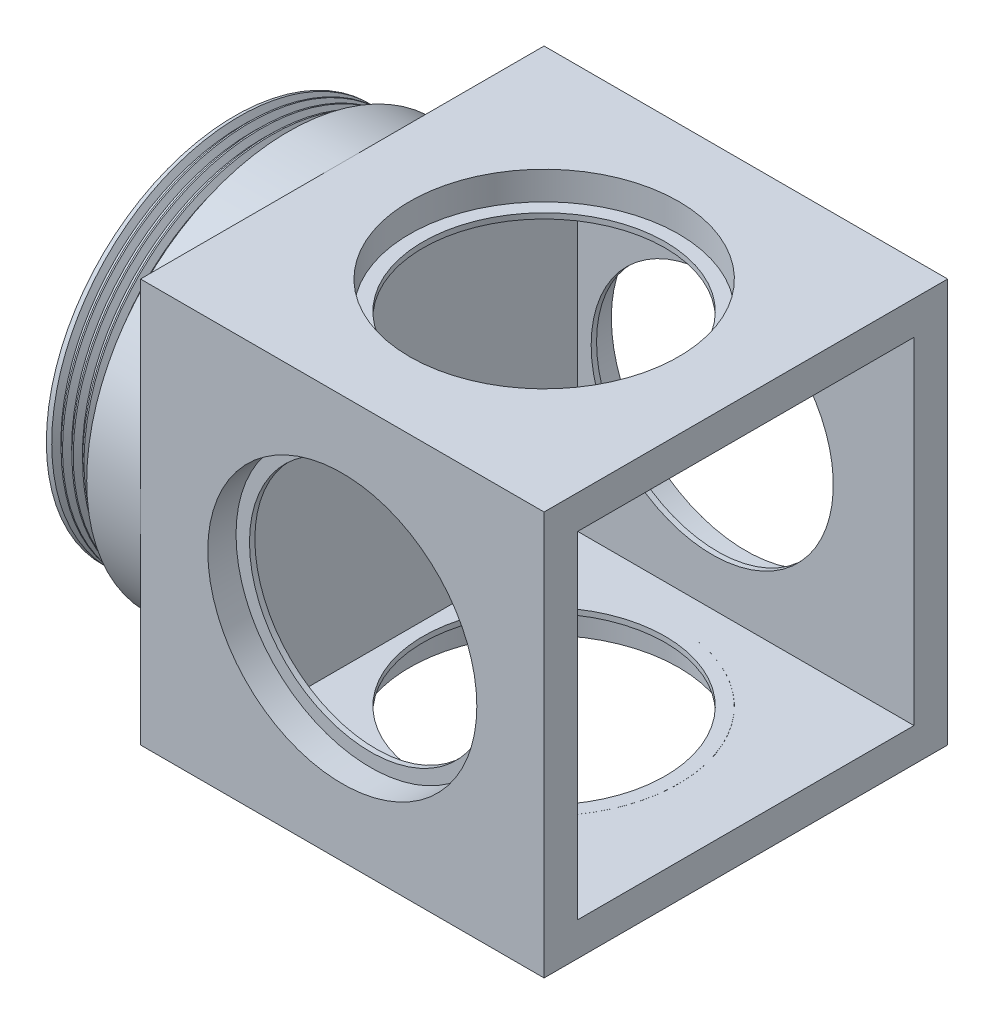
SolidWorks part; units mm, degrees
ref_plane "Front Plane" through (0, 0, 0) normal (0, 0, 1) x (1, 0, 0)
ref_plane "Top Plane" through (0, 0, 0) normal (0, 1, 0) x (1, 0, 0)
ref_plane "Right Plane" through (0, 0, 0) normal (1, 0, 0) x (0, 0, -1)
sketch "Sketch1" plane through (0, 0, 0) normal (0, 0, 1) x (1, 0, 0)
  line L1 (-37.5, -37.5) -> (37.5, -37.5)
  line L2 (-37.5, -37.5) -> (-37.5, 37.5)
  line L3 (-37.5, 37.5) -> (37.5, 37.5)
  line L4 (37.5, -37.5) -> (37.5, 37.5)
  line L5 (-37.5, -37.5) -> (37.5, 37.5) construction
  line L6 (-37.5, 37.5) -> (37.5, -37.5) construction
  line L11 (-25, -25) -> (25, 25) construction
  line L12 (-25, 25) -> (25, -25) construction
  circle A1 centre (0, 0) radius 25
  point P0 (0, 0)
  point P6 (0, 0)
  dimension "D3" = 50
  dimension "D1" = 75
  dimension "D2" = 50
extrude "Boss-Extrude1" add sketch "Sketch1" along normal mid plane 75
sketch "Sketch2" plane through (0, 37.5, 0) normal (0, 1, 0) x (1, 0, 0)
  circle A0 centre (0.0169, 0) radius 25
  point P0 (0, 0)
  dimension "D2" = 50
extrude "Cut-Extrude1" cut sketch "Sketch2" against normal up to surface (75 mm away) up to face at (0, -37.5, 0)
sketch "Sketch3" plane through (37.5, 0, 0) normal (1, 0, 0) x (0, 0, -1)
  line L1 (-31.25, -31.25) -> (31.25, -31.25)
  line L2 (-31.25, -31.25) -> (-31.25, 31.25)
  line L3 (-31.25, 31.25) -> (31.25, 31.25)
  line L4 (31.25, -31.25) -> (31.25, 31.25)
  line L5 (-31.25, -31.25) -> (31.25, 31.25) construction
  line L6 (-31.25, 31.25) -> (31.25, -31.25) construction
  point P0 (0, 0)
  dimension "D1" = 62.5
extrude "Cut-Extrude2" cut sketch "Sketch3" against normal blind 62.5
sketch "Sketch4" plane through (-37.5, 0, 0) normal (-1, 0, 0) x (0, 0, 1)
  circle A0 centre (0, 0) radius 37.5
extrude "Boss-Extrude2" add sketch "Sketch4" along normal blind 10
sketch "Sketch5" plane through (-47.5, 0, 0) normal (-1, 0, 0) x (0, 0, 1)
  circle A0 centre (0, 0) radius 32.5
  circle A1 centre (0, 0) radius 35
  dimension "D1" = 65
  dimension "D2" = 70
extrude "Boss-Extrude3" add sketch "Sketch5" along normal blind 10
thread "Thread1" pitch 2 method cut profile "Thread Profile1" start angle 0, offset 0, length 0, pitch 2, diameter 70
ref_plane "Plane1" through (-57.5, 0, -35) normal (0, -1, 0) x (0, 0, -1)
sketch "Thread Profile1" plane through (-57.5, 0, -35) normal (0, -1, 0) x (0, 0, -1)
  line L0 (0, 0) -> (0, 2) construction
  line L11 (0, 0) -> (0, 1.75)
  line L12 (0, 1.75) -> (-1.0825, 1.125)
  line L13 (-1.0825, 1.125) -> (-1.0825, 0.625)
  line L15 (-1.0825, 0.625) -> (0, 0)
  line L17 (-1.0825, 0.875) -> (0, 0.875) construction
  point P2 (0, 0)
  dimension "Pitch" = 2
  dimension "Profile_Angle" = 60
  dimension "Profile_Land" = 0.5
  dimension "Profile_Height" = 1.0825
sketch "Sketch6" plane through (0, -37.5, 0) normal (0, -1, 0) x (-1, 0, 0)
  circle A0 centre (0, 0) radius 22.5
  circle A1 centre (0, 0) radius 25
  dimension "D1" = 45
  dimension "D2" = 50
extrude "Boss-Extrude4" add sketch "Sketch6" along normal blind 1 from surface starting at face at (6.25, -31.25, 0)
sketch "Sketch7" plane through (0, 0, -37.5) normal (0, 0, -1) x (-1, 0, 0)
  circle A0 centre (0, 0) radius 25
  circle A1 centre (0, 0) radius 22.5
  dimension "D1" = 50
  dimension "D2" = 45
extrude "Boss-Extrude5" add sketch "Sketch7" along normal blind 1 from surface contours A0 | A1 starting at face at (-4.1667, 0, -31.25)
sketch "Sketch9" plane through (0, 31.25, 0) normal (0, -1, 0) x (1, 0, 0)
  circle A0 centre (0, 0) radius 25
  circle A1 centre (0, 0) radius 22.5
  dimension "D1" = 45
  dimension "D2" = 50
extrude "Boss-Extrude6" add sketch "Sketch9" against normal blind 1
sketch "Sketch10" plane through (0, 0, 31.25) normal (0, 0, -1) x (-1, 0, 0)
  circle A0 centre (0, 0) radius 25
  circle A1 centre (0, 0) radius 22.5
  dimension "D1" = 50
  dimension "D2" = 45
extrude "Boss-Extrude7" add sketch "Sketch10" against normal blind 1 separate body contours A0 | A1
